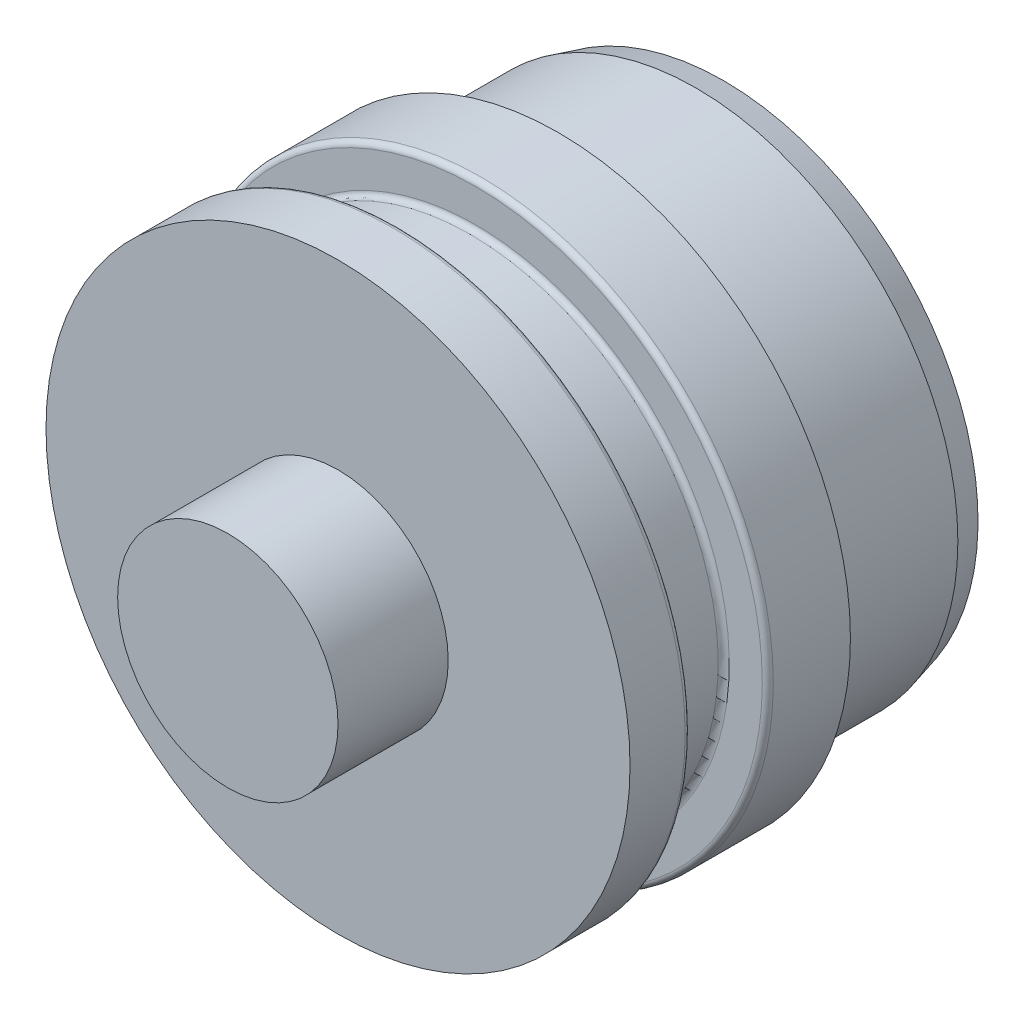
SolidWorks part; units mm, degrees
material "PET-P _ White"
ref_plane "Front Plane" through (0, 0, 0) normal (0, 0, 1) x (1, 0, 0)
ref_plane "Top Plane" through (0, 0, 0) normal (0, 1, 0) x (1, 0, 0)
ref_plane "Right Plane" through (0, 0, 0) normal (1, 0, 0) x (0, 0, -1)
ref_axis "Axis2" through (0, 0, -17.6438) along (0, 0, -1)
sketch "Sketch1" plane through (0, 0, 0) normal (1, 0, 0) x (0, 0, -1)
  line L0 (0, 5.08) -> (0, 13.462)
  line L1 (0, 13.462) -> (2.794, 13.462)
  line L2 (2.794, 13.462) -> (2.794, 11.43)
  line L3 (2.794, 11.43) -> (6.35, 11.43)
  line L4 (6.35, 11.43) -> (6.35, 13.462)
  line L5 (6.35, 13.462) -> (10.16, 13.462)
  line L6 (10.16, 13.462) -> (10.16, 12.065)
  line L7 (17.78, 6.731) -> (5.08, 6.731)
  line L8 (5.08, 0) -> (0, 0)
  line L9 (5.08, 6.731) -> (5.08, 0)
  line L10 (0, 5.08) -> (-5.08, 5.08)
  line L11 (10.16, 12.065) -> (17.78, 12.065)
  line L12 (17.78, 12.065) -> (17.78, 6.731)
  line L13 (-5.08, 5.08) -> (-5.08, 0)
  line L14 (17.6438, 0) -> (23.1226, 0) construction
  line L15 (-5.08, 0) -> (0, 0)
  dimension "D13" = 5.08
  dimension "D1" = 13.462
  dimension "D2" = 26.924
  dimension "D3" = 22.86
  dimension "D4" = 3.556
  dimension "D5" = 7.62
  dimension "D6" = 3.81
  dimension "D7" = 12.7
  dimension "D8" = 17.78
  dimension "D9" = 24.13
  dimension "D10" = 2.794
  dimension "D11" = 11.43
  dimension "D12" = 5.08
revolve "Revolve1" add sketch "Sketch1" angle 360 about L8
chamfer "Chamfer1" distance 1.27 angle 15 1 edges at (0, 12.065, -17.78) first distance on face at (0, 12.065, -10.16)
fillet "Fillet1" radius 0.254 4 edges at (0, 13.462, -2.794) (0, 11.43, -2.794) (0, 11.43, -6.35) (0, 13.462, -6.35)
